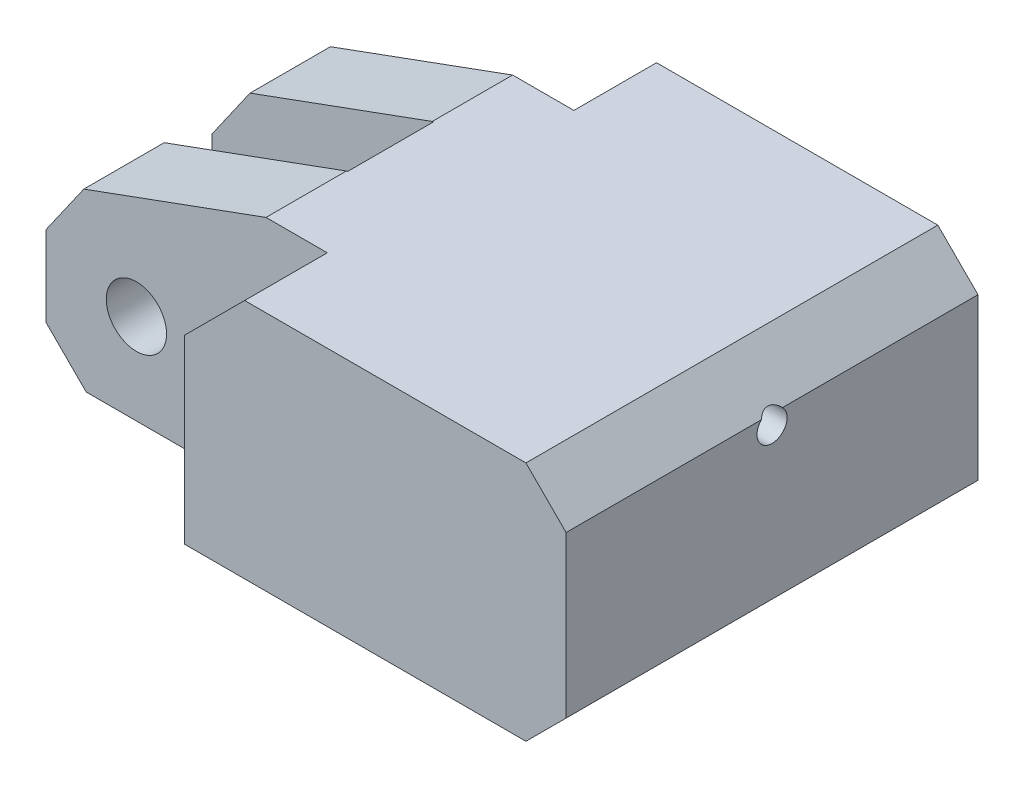
SolidWorks part; units mm, degrees
ref_plane "Спереди" through (0, 0, 0) normal (0, 0, 1) x (1, 0, 0)
ref_plane "Сверху" through (0, 0, 0) normal (0, 1, 0) x (1, 0, 0)
ref_plane "Справа" through (0, 0, 0) normal (1, 0, 0) x (0, 0, -1)
sketch "Эскиз2" plane through (0, 0, 0) normal (1, 0, 0) x (0, 0, -1)
  line L1 (-10.25, 6) -> (10.25, 6)
  line L2 (-10.25, 6) -> (-10.25, -6)
  line L3 (-10.25, -6) -> (10.25, -6)
  line L4 (10.25, 6) -> (10.25, -6)
  line L5 (-10.25, 6) -> (10.25, -6) construction
  line L6 (-10.25, -6) -> (10.25, 6) construction
  point P0 (0, 0)
extrude "Вытянуть1" add sketch "Эскиз2" along normal blind 30
sketch "Эскиз3" plane through (0, 6, 0) normal (0, 1, 0) x (1, 0, 0)
  line L0 (0, 0) -> (-9.2006, 0) construction
  line L1 (0, 10.25) -> (0, -10.25) construction
  line L2 (-11, 2.1371) -> (11, 2.1371)
  line L3 (-11, 2.1371) -> (-11, -2.1371)
  line L4 (-11, -2.1371) -> (11, -2.1371)
  line L5 (11, 2.1371) -> (11, -2.1371)
  line L6 (-11, 2.1371) -> (11, -2.1371) construction
  line L7 (-11, -2.1371) -> (11, 2.1371) construction
  point P1 (0, 0)
  dimension "D1" = 11
extrude "Вырез-Вытянуть1" cut sketch "Эскиз3" against normal through all
sketch "Эскиз10" plane through (0, 6, 0) normal (0, 1, 0) x (1, 0, 0)
  line L0 (5.6157, 0) -> (-3.5713, 0) construction
  line L1 (0, 10.25) -> (0, 2.1371) construction
  line L2 (11, 2.1371) -> (0, 2.1371) construction
  line L3 (-6.1065, 15.2007) -> (11, 15.2007)
  line L4 (-6.1065, 15.2007) -> (-6.1065, 6.1371)
  line L5 (-6.1065, 6.1371) -> (11, 6.1371)
  line L6 (11, 15.2007) -> (11, 6.1371)
  line L7 (-6.1065, -15.2007) -> (11, -15.2007)
  line L8 (-6.1065, -15.2007) -> (-6.1065, -6.1371)
  line L9 (-6.1065, -6.1371) -> (11, -6.1371)
  line L10 (11, -15.2007) -> (11, -6.1371)
  dimension "D1" = 4
  dimension "D2" = 11
extrude "Вырез-Вытянуть3" cut sketch "Эскиз10" against normal through all
sketch "Эскиз11" plane through (0, 0, 6.1371) normal (0, 0, 1) x (1, 0, 0)
  line L0 (0, -6) -> (0, 6) construction
  line L2 (11, -6) -> (0, -6) construction
  circle A0 centre (4.5, -1.5) radius 1.5
  dimension "D1" = 4.5
  dimension "D2" = 4.5
extrude "Вытянуть6" cut sketch "Эскиз11" against normal through all
sketch "Эскиз12" plane through (11, 0, 0) normal (-1, 0, 0) x (0, 0, 1)
  circle A0 centre (-1.7914, -3.4073) radius 0.75
extrude "Вырез-Вытянуть4" cut sketch "Эскиз12" against normal blind 12
sketch "Эскиз13" plane through (0, 0, 10.25) normal (0, 0, 1) x (1, 0, 0)
  line L0 (10.95, 6) -> (0, 6)
  line L1 (30, 6) -> (11, 6) construction
  line L2 (0, -6) -> (0, 6) construction
  line L3 (0, 6) -> (0, 2)
  line L4 (0, 2) -> (10.95, 6)
  line L6 (40.0058, 6) -> (40.0058, 2)
  line L7 (11, 6) -> (0, 6) construction
  line L8 (40.0058, 2) -> (30.0058, 6)
  line L9 (30.0058, 6) -> (40.0058, 6)
  dimension "D2" = 4
  dimension "D1" = 10.95
  dimension "D3" = 10
extrude "Вытянуть7" cut sketch "Эскиз13" against normal through all
chamfer "Фаска5" distance 2 angle 45 4 edges at (0, -6, 4.1371) (0, -6, -4.1371) (30, -6, 0) (30, 6, 0)
chamfer "Фаска6" distance 2 angle 35 2 edges at (0, 2, 4.1371) (0, 2, -4.1371) first distance on face at (0, -1, 4.1371) first distance on face at (0, -1, -4.1371)
sketch "Эскиз14" plane through (11, 0, 0) normal (-1, 0, 0) x (0, 0, 1)
  circle A0 centre (0, 3.4654) radius 0.75
extrude "Вырез-Вытянуть5" cut sketch "Эскиз14" against normal through all
chamfer "Фаска8" distance 3 angle 45 2 edges at (11, 6, 8.1936) (11, 6, -8.1936)
sketch "Эскиз15" plane through (0, -6, 0) normal (0, -1, 0) x (1, 0, 0)
  line L0 (11, 10.25) -> (11, 6.1371) construction
  line L1 (16, 6.25) -> (25, 6.25)
  line L2 (14, 4.25) -> (14, -4.25)
  line L3 (16, -6.25) -> (25, -6.25)
  line L4 (27, 4.25) -> (27, -4.25)
  line L5 (28, 10.25) -> (11, 10.25) construction
  line L6 (28, -10.25) -> (11, -10.25) construction
  line L7 (30, 10.25) -> (30, -10.25) construction
  arc A0 (16, 6.25) -> (14, 4.25) centre (16, 4.25) ccw
  arc A1 (27, 4.25) -> (25, 6.25) centre (25, 4.25) ccw
  arc A2 (25, -6.25) -> (27, -4.25) centre (25, -4.25) ccw
  arc A3 (16, -6.25) -> (14, -4.25) centre (16, -4.25) cw
  dimension "D5" = 2
  dimension "D1" = 3
  dimension "D2" = 4
  dimension "D3" = 4
  dimension "D4" = 3
extrude "Вытянуть8" cut sketch "Эскиз15" against normal blind 10
